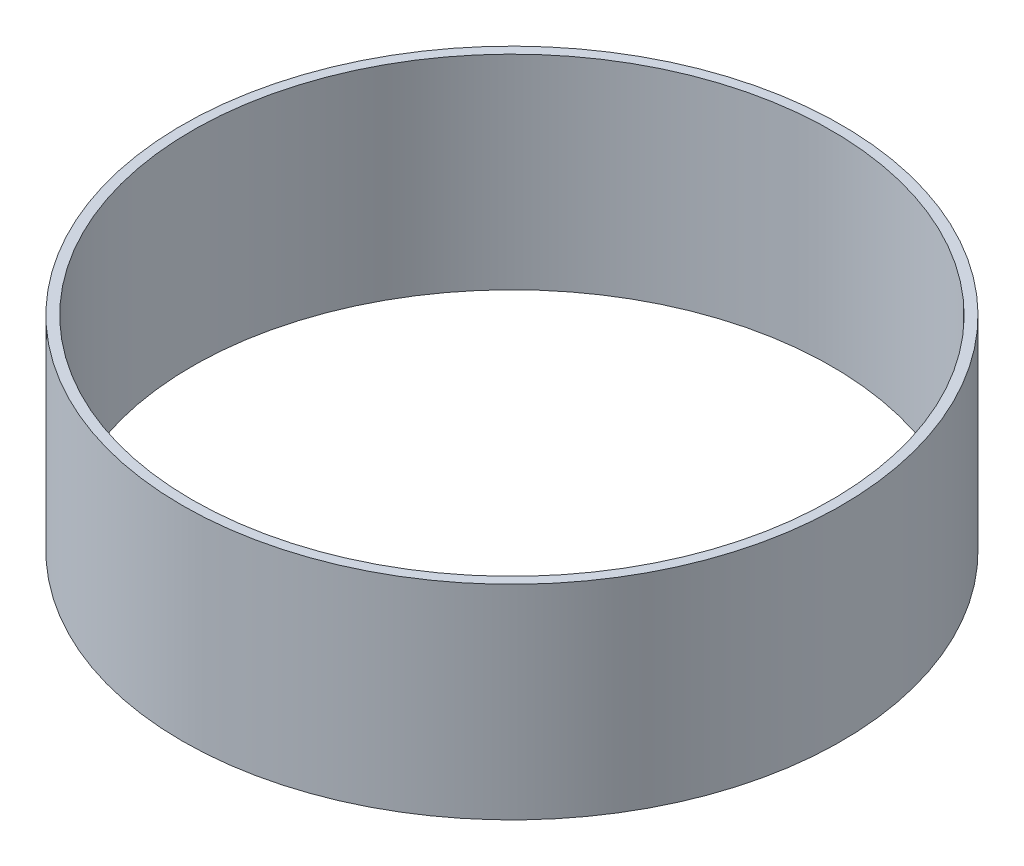
SolidWorks part; units mm, degrees
material "A-Glass Fiber"
ref_plane "Front Plane" through (0, 0, 0) normal (0, 0, 1) x (1, 0, 0)
ref_plane "Top Plane" through (0, 0, 0) normal (0, 1, 0) x (1, 0, 0)
ref_plane "Right Plane" through (0, 0, 0) normal (1, 0, 0) x (0, 0, -1)
sketch "Sketch1" plane through (0, 0, 0) normal (0, 1, 0) x (1, 0, 0)
  circle A0 centre (0, 0) radius 78.35
  circle A1 centre (0, 0) radius 80.75
  dimension "D1" = 156.7
  dimension "D2" = 2.4
extrude "Boss-Extrude1" add sketch "Sketch1" along normal blind 25 and the other way blind 25
